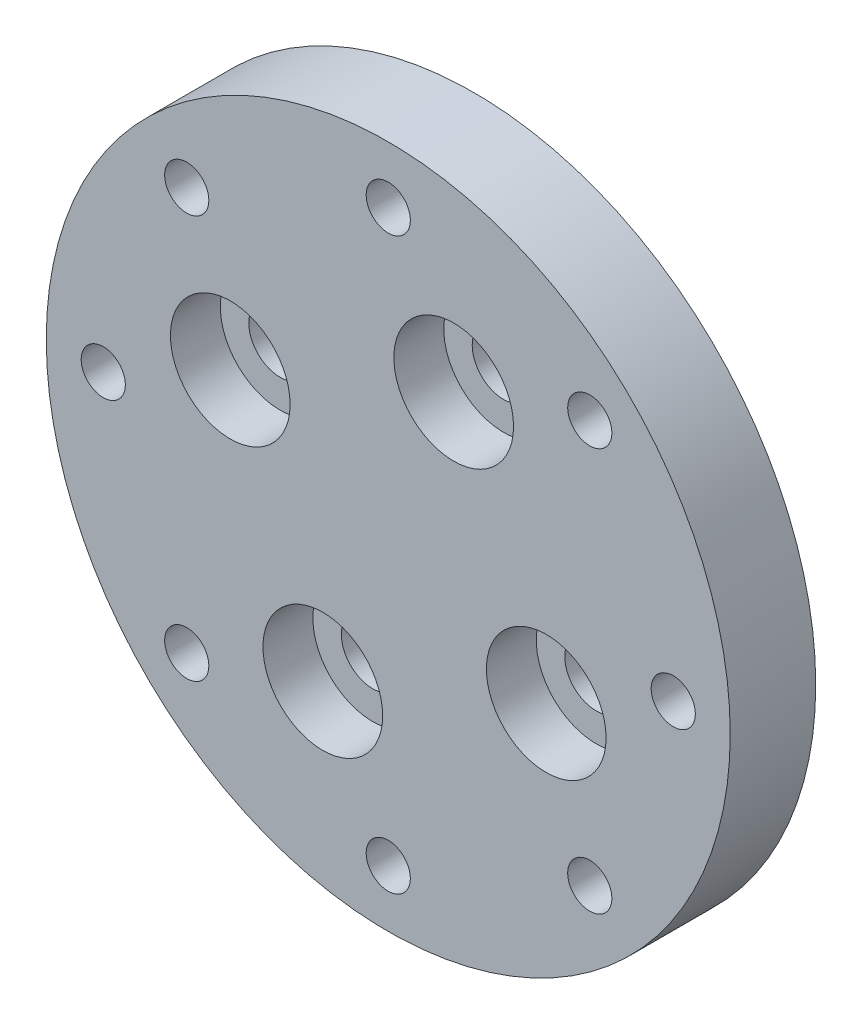
SolidWorks part; units mm, degrees
ref_plane "Front Plane" through (0, 0, 0) normal (0, 0, 1) x (1, 0, 0)
ref_plane "Top Plane" through (0, 0, 0) normal (0, 1, 0) x (1, 0, 0)
ref_plane "Right Plane" through (0, 0, 0) normal (1, 0, 0) x (0, 0, -1)
ref_axis "Axis1" through (0, 0, 5.5) along (0, 0, -1)
sketch "Sketch6" plane through (0, 0, 0) normal (0, 0, 1) x (1, 0, 0)
  circle A0 centre (0, 0) radius 24
extrude "Boss-Extrude1" add sketch "Sketch6" along normal blind 6
sketch "Sketch8" plane through (0, 0, 0) normal (0, 0, -1) x (-1, 0, 0)
  line L0 (0, 20) -> (0, 0) construction
  line L1 (0, 0) -> (11.0866, 4.5922) construction
  circle A0 centre (0, 20) radius 1.55
  circle A1 centre (14.1421, 14.1421) radius 1.55
  circle A2 centre (20, 0) radius 1.55
  circle A3 centre (14.1421, -14.1421) radius 1.55
  circle A4 centre (0, -20) radius 1.55
  circle A5 centre (-14.1421, -14.1421) radius 1.55
  circle A6 centre (-20, 0) radius 1.55
  circle A7 centre (-14.1421, 14.1421) radius 1.55
  circle A8 centre (0, 0) radius 12 construction
  circle A13 centre (11.0866, 4.5922) radius 2.2
  circle A14 centre (4.5922, -11.0866) radius 2.2
  circle A15 centre (-11.0866, -4.5922) radius 2.2
  circle A16 centre (-4.5922, 11.0866) radius 2.2
  point P30 (0, 0)
  point P31 (0, 0)
  dimension "D1" = 8
  dimension "D2" = 4
extrude "Cut-Extrude6" cut sketch "Sketch8" against normal up to surface (6 mm away) up to face at (24, 0, 6)
sketch "Sketch11" plane through (0, 0, 6) normal (0, 0, 1) x (1, 0, 0)
  circle A8 centre (-11.0866, 4.5922) radius 4.2
  circle A9 centre (4.5922, 11.0866) radius 4.2
  circle A10 centre (11.0866, -4.5922) radius 4.2
  circle A11 centre (-4.5922, -11.0866) radius 4.2
  point P19 (0, 0)
  point P30 (0, 0)
  dimension "D2" = 4
extrude "Cut-Extrude7" cut sketch "Sketch11" against normal blind 3.5
sketch "Sketch12" plane through (0, 0, 0) normal (0, 0, -1) x (-1, 0, 0)
  circle A0 centre (0, 20) radius 3.5
  circle A1 centre (14.1421, 14.1421) radius 3.5
  circle A2 centre (20, 0) radius 3.5
  circle A3 centre (14.1421, -14.1421) radius 3.5
  circle A4 centre (0, -20) radius 3.5
  circle A5 centre (-14.1421, -14.1421) radius 3.5
  circle A6 centre (-20, 0) radius 3.5
  circle A7 centre (-14.1421, 14.1421) radius 3.5
  point P19 (0, 0)
  dimension "D1" = 8
extrude "Cut-Extrude8" cut sketch "Sketch12" against normal blind 3
